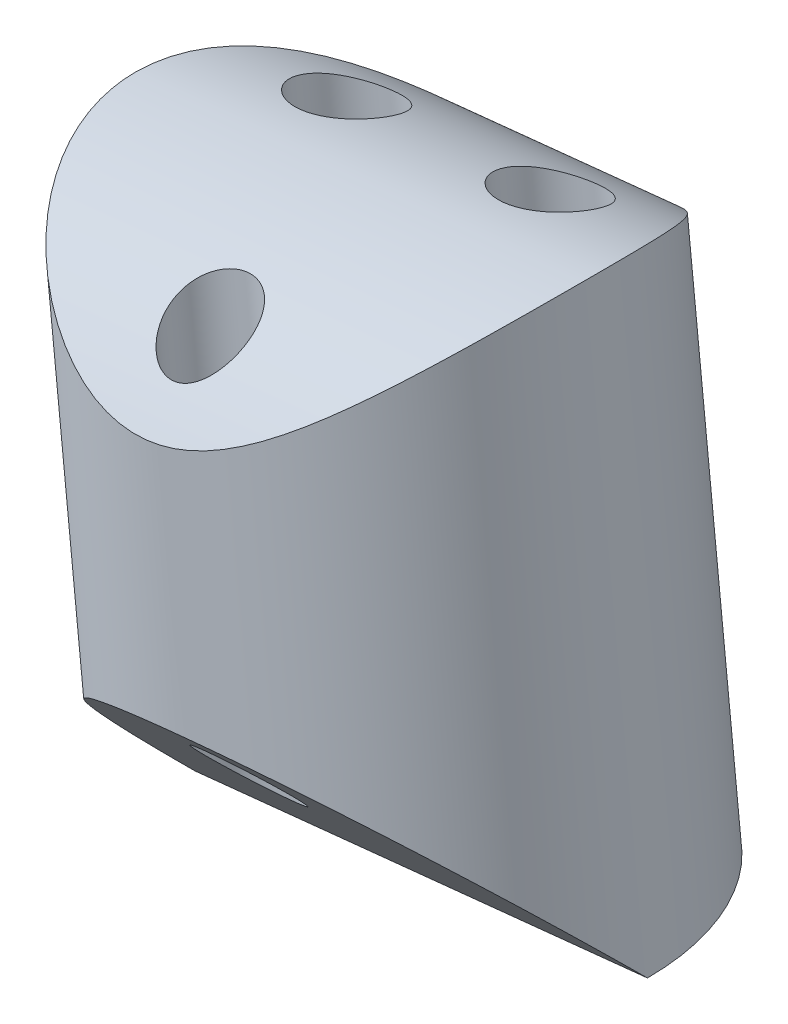
SolidWorks part; units mm, degrees
ref_plane "Front Plane" through (0, 0, 0) normal (0, 0, 1) x (1, 0, 0)
ref_plane "Top Plane" through (0, 0, 0) normal (0, 1, 0) x (1, 0, 0)
ref_plane "Right Plane" through (0, 0, 0) normal (1, 0, 0) x (0, 0, -1)
sketch "Sketch2" plane through (0, 0, 0) normal (0, 0, 1) x (1, 0, 0)
  line L0 (0, 0) -> (90, 0)
  line L1 (90, 0) -> (90, 120)
  line L2 (90, 120) -> (0, 120)
  line L3 (0, 120) -> (0, 0)
  line L4 (0, 120) -> (-10, 120)
  line L5 (-10, 120) -> (-10, 16.9491)
  line L6 (-10, 120) -> (57.5, 127)
  line L7 (57.5, 127) -> (90, 124)
  line L8 (90, 120) -> (99, 60)
  line L10 (90, 124) -> (90, 120)
  line L11 (5.9147, 0) -> (5.9147, -25)
  line L12 (5.9147, -25) -> (-4.0853, -25)
  line L13 (-4.0853, -29) -> (-4.0853, 0)
  line L14 (80, 0) -> (80, -25)
  line L15 (80, -25) -> (90, -25)
  line L16 (90, -29) -> (90, 0)
  line L17 (15.7927, 122.6748) -> (5.4776, 222.1414)
  line L18 (5.4776, 222.1414) -> (21.3923, 223.7918)
  line L19 (21.3923, 223.7918) -> (31.7073, 124.3252)
  line L20 (7.6492, 201.201) -> (23.5639, 202.8514)
  line L21 (10.9066, 169.7905) -> (26.8212, 171.441)
  line L22 (-10, 120) -> (-20.0396, 216.8108)
  line L23 (-20.0396, 216.8108) -> (-4.125, 218.4612)
  line L24 (-4.125, 218.4612) -> (5.9147, 121.6504)
  line L25 (-17.926, 196.4296) -> (-2.0114, 198.08)
  line L26 (-14.7556, 165.8578) -> (1.159, 167.5082)
  line L27 (57.5, 127) -> (46.9095, 229.1223)
  line L28 (46.9095, 229.1223) -> (30.9949, 227.4719)
  line L29 (30.9949, 227.4719) -> (41.5853, 125.3496)
  line L30 (33.2245, 205.9725) -> (49.1391, 207.6229)
  line L31 (36.5688, 173.7233) -> (52.4835, 175.3737)
  line L34 (90, 124) -> (99.1917, 223.5767)
  line L35 (99.1917, 223.5767) -> (83.2594, 225.0473)
  line L36 (83.2594, 225.0473) -> (74.0677, 125.4707)
  line L38 (81.3243, 204.0838) -> (97.2566, 202.6132)
  line L39 (78.4217, 172.6386) -> (94.354, 171.1679)
  line L40 (62.4078, 79.6749) -> (57.5, 127) construction
  line L41 (41.5853, 125.3496) -> (46.4931, 78.0244) construction
  line L42 (46.4931, 78.0244) -> (62.4078, 79.6749) construction
  line L43 (31.7073, 124.3252) -> (36.6151, 77.0001) construction
  line L44 (36.6151, 77.0001) -> (20.7005, 75.3496) construction
  line L45 (20.7005, 75.3496) -> (15.7927, 122.6748) construction
  line L46 (5.9147, 121.6504) -> (10.8224, 74.3253) construction
  line L47 (10.8224, 74.3253) -> (-5.0922, 72.6749) construction
  line L48 (-5.0922, 72.6749) -> (-10, 120) construction
  line L49 (74.0677, 125.4707) -> (69.6944, 78.0931) construction
  line L50 (69.6944, 78.0931) -> (85.7624, 78.0931) construction
  line L51 (85.7624, 78.0931) -> (90, 124) construction
  line L52 (-12.0823, 217.636) -> (10.4873, 0) construction
  line L53 (13.4349, 222.9666) -> (36.5574, 0) construction
  line L54 (38.9522, 228.2971) -> (62.6275, 0) construction
  line L55 (91.2256, 224.312) -> (70.5198, 0) construction
  line L59 (99, 60) -> (93.5277, 44.9649)
  line L60 (99, 60) -> (169.4769, 34.3485)
  line L61 (169.4769, 34.3485) -> (164.0046, 19.3134)
  line L62 (164.0046, 19.3134) -> (93.5277, 44.9649)
  line L63 (90, -2) -> (100, -2)
  line L64 (141.2862, 44.6091) -> (135.8138, 29.574)
  line L65 (99, 60) -> (55.7741, 75.7329) construction
  line L66 (55.7741, 75.7329) -> (50.3018, 60.6978) construction
  line L67 (100, -2) -> (100, -29)
  line L70 (-4.0853, -2) -> (-14.0853, -2)
  line L71 (-14.0853, -2) -> (-14.0853, -29)
  line L74 (-4.0853, 0) -> (0, 0)
  line L75 (-14.0853, -29) -> (-14.0853, -112.587)
  line L76 (-14.0853, -112.587) -> (100, -112.587)
  line L77 (100, -112.587) -> (100, -29)
  line L78 (-14.0853, -29) -> (100, -29)
  line L79 (-14.0853, -14.5) -> (100, -14.5) construction
  line L80 (31.7073, -112.587) -> (31.7073, -122.6232)
  line L81 (31.7073, -122.6232) -> (42.9573, -122.6232)
  line L82 (42.9573, -122.6232) -> (42.9573, -112.587)
  line L83 (-14.0853, -112.587) -> (-88.3667, -112.587)
  line L84 (-88.3667, -112.587) -> (-88.3667, -128.2699)
  line L85 (-88.3667, -128.2699) -> (169.4958, -128.2699)
  line L86 (169.4958, -128.2699) -> (169.4958, -112.587)
  line L87 (169.4958, -112.587) -> (100, -112.587)
  line L88 (90, 60) -> (-10, 60) construction
  line L89 (50.3018, 60.6978) -> (93.5277, 44.9649) construction
  line L90 (87.2806, 55.7521) -> (166.7408, 26.8309) construction
  line L91 (87.2806, 55.7521) -> (82.1749, 52.5336) construction
  line L92 (82.1749, 52.5336) -> (77.3257, 0) construction
  line L93 (83.1185, 56.6957) -> (86.337, 51.59) construction
  arc A0 (-10, 16.9491) -> (-4.0853, 0) centre (14.9876, 16.1624) ccw
  arc A1 (93.5277, 44.9649) -> (90, 0) centre (-126.4069, 39.5988) cw
  point P42 (41.1818, 206.7977)
  point P100 (84.7278, 54.1428)
  point P101 (84.7278, 54.1428)
  dimension "D11" = 47.3684
  dimension "D35" = 9
  dimension "D32" = 220
  dimension "D36" = 25
  dimension "D1" = 120
  dimension "D2" = 90
  dimension "D3" = 10
  dimension "D5" = 67.862
  dimension "D6" = 7
  dimension "D7" = 4
  dimension "D8" = 16
  dimension "D9" = 16
  dimension "D10" = 100
  dimension "D12" = 31.5789
  dimension "D13" = 16
  dimension "D14" = 16
  dimension "D15" = 16
  dimension "D16" = 25.7927
  dimension "D17" = 100
  dimension "D18" = 21.0526
  dimension "D19" = 31.5789
  dimension "D20" = 97.33
  dimension "D21" = 102.67
  dimension "D22" = 20.4905
  dimension "D23" = 30.7358
  dimension "D24" = 21.6147
  dimension "D25" = 32.4221
  dimension "D26" = 25
  dimension "D28" = 25
  dimension "D29" = 75
  dimension "D30" = 47.5789
  dimension "D31" = 30
  dimension "D33" = 46
  dimension "D34" = 20
  dimension "D37" = 2
  dimension "D38" = 2
  dimension "D39" = 27
  dimension "D40" = 10
  dimension "D41" = 10
  dimension "D42" = 27
  dimension "D43" = 14.5
  dimension "D44" = 127.5
ref_plane "Plane1" through (87.2806, 55.7521, 0) normal (-0.846, -0.5333, 0) x (0, 0, 1)
ref_plane "Plane2" through (82.1749, 52.5336, 0) normal (-0.0919, -0.9958, 0) x (-0.9958, 0.0919, 0)
ref_plane "Plane3" through (91.2256, 224.312, 0) normal (-0.0919, -0.9958, 0) x (-0.9958, 0.0919, 0)
ref_plane "Plane4" through (38.9522, 228.2971, 0) normal (0.1032, -0.9947, 0) x (-0.9947, -0.1032, 0)
ref_plane "Plane5" through (13.4349, 222.9666, 0) normal (0.1032, -0.9947, 0) x (-0.9947, -0.1032, 0)
ref_plane "Plane7" through (166.7408, 26.8309, 0) normal (0.9397, -0.342, 0) x (0, 0, -1)
ref_plane "Plane8" through (110.4217, -40.1902, 0) normal (0.9397, -0.342, 0) x (0, 0, -1)
ref_plane "Plane9" through (19.3664, 209.803, 0) normal (-0.0919, -0.9958, 0) x (-0.9958, 0.0919, 0)
ref_plane "Plane10" through (16.4638, 178.3578, 0) normal (-0.0919, -0.9958, 0) x (-0.9958, 0.0919, 0)
ref_plane "Plane11" through (-20.7793, 200.3721, 0) normal (0.1032, -0.9947, 0) x (-0.9947, -0.1032, 0)
ref_plane "Plane12" through (-17.435, 168.1229, 0) normal (0.1032, -0.9947, 0) x (-0.9947, -0.1032, 0)
ref_plane "Plane13" through (-20.5619, 198.2754, 0) normal (0.1032, -0.9947, 0) x (-0.9947, -0.1032, 0)
ref_plane "Plane14" through (-17.3045, 166.8649, 0) normal (0.1032, -0.9947, 0) x (-0.9947, -0.1032, 0)
ref_plane "Plane15" through (-12.0823, 217.636, 0) normal (0.1032, -0.9947, 0) x (-0.9947, -0.1032, 0)
ref_plane "Plane16" through (-20.3445, 196.1788, 0) normal (0.1032, -0.9947, 0) x (-0.9947, -0.1032, 0)
ref_plane "Plane17" through (-17.1741, 165.607, 0) normal (0.1032, -0.9947, 0) x (-0.9947, -0.1032, 0)
ref_plane "Plane18" through (12.1098, 131.1899, 0) normal (-0.0919, -0.9958, 0) x (-0.9958, 0.0919, 0)
ref_plane "Plane19" through (-12.4184, 119.7492, 0) normal (0.1032, -0.9947, 0) x (-0.9947, -0.1032, 0)
ref_plane "Plane20" through (0, 0, 0) normal (0, 0, 1) x (0.1032, -0.9947, 0)
ref_plane "Plane21" through (0, 0, 0) normal (0, 0, 1) x (-0.0919, -0.9958, 0)
ref_plane "Plane22" through (10.3758, 1.076, 0) normal (-0.9947, -0.1032, 0) x (0.1032, -0.9947, 0)
ref_plane "Plane23" through (36.1684, 3.7508, 0) normal (-0.9947, -0.1032, 0) x (0.1032, -0.9947, 0)
ref_plane "Plane24" through (61.9611, 6.4256, 0) normal (-0.9947, -0.1032, 0) x (0.1032, -0.9947, 0)
ref_plane "Plane25" through (69.924, -6.4545, 0) normal (-0.9958, 0.0919, 0) x (-0.0919, -0.9958, 0)
sketch "Sketch3" plane through (-12.0823, 217.636, 0) normal (0.1032, -0.9947, 0) x (-0.9947, -0.1032, 0)
  circle A0 centre (0, 0) radius 8
  dimension "D1" = 16
extrude "Boss-Extrude1" add sketch "Sketch3" along normal blind 20.4905
sketch "Sketch4" plane through (10.3758, 1.076, 0) normal (-0.9947, -0.1032, 0) x (0.1032, -0.9947, 0)
  line L0 (-217.7214, 8) -> (-213.7214, 8)
  line L1 (-197.2309, 8) -> (-217.7214, 8) construction
  line L2 (-217.7214, 8) -> (-217.7214, -8)
  line L3 (-217.7214, -8) -> (-213.7214, -8)
  line L4 (-217.7214, -8) -> (-197.2309, -8) construction
  arc A0 (-213.7214, 8) -> (-213.7214, -8) centre (-207.3937, 0) ccw
  dimension "D2" = 10.2
  dimension "D1" = 4
extrude "Cut-Extrude1" cut sketch "Sketch4" against normal through all and the other way through all
sketch "Sketch5" plane through (10.3758, 1.076, 0) normal (-0.9947, -0.1032, 0) x (0.1032, -0.9947, 0)
  line L0 (-197.2309, 0) -> (-205.2309, 8)
  line L1 (-197.2309, -8) -> (-197.2309, 8) construction
  line L2 (-197.2309, 8) -> (-213.7214, 8) construction
  line L3 (-205.2309, 8) -> (-197.2309, 8)
  line L4 (-197.2309, 8) -> (-197.2309, 0)
  dimension "D1" = 45
extrude "Cut-Extrude2" cut sketch "Sketch5" against normal through all and the other way through all
sketch "Sketch7" plane through (10.3758, 1.076, 0) normal (-0.9947, -0.1032, 0) x (0.1032, -0.9947, 0)
  line L2 (-193.2309, 0) -> (-197.2309, -4)
  line L5 (-201.2309, 4) -> (-197.2309, 0)
  line L6 (-197.2309, 0) -> (-205.2309, 8) construction
  line L8 (-213.7055, 0) -> (7.2742, 0) construction
  line L9 (-193.2309, 0) -> (-193.2309, 4)
  line L10 (-193.2309, 4) -> (-201.2309, 4)
  line L11 (-197.2309, 0) -> (-193.2309, 4) construction
  line L12 (-197.2309, -8) -> (-197.2309, 0) construction
  line L13 (-197.2309, 0) -> (-197.2309, -4)
  dimension "D1" = 45
sketch "Sketch8" plane through (-12.0823, 217.636, 0) normal (0.1032, -0.9947, 0) x (-0.9947, -0.1032, 0)
  line L0 (8, 0) -> (-8, 0) construction
  circle A0 centre (-3.6, 3) radius 1.6
  circle A1 centre (3.6, 3) radius 1.6
  circle A3 centre (0, -5.5) radius 1.4
  point P6 (0, 0)
  dimension "D1" = 3.2
  dimension "D2" = 3.2
  dimension "D7" = 2.8
  dimension "D3" = 3
  dimension "D4" = 3
  dimension "D5" = 3.6
  dimension "D6" = 3.6
  dimension "D8" = 5.5
extrude "Cut-Extrude3" cut sketch "Sketch8" against normal through all and the other way through all
sketch "Sketch9" plane through (-20.3445, 196.1788, 0) normal (0.1032, -0.9947, 0) x (0.9947, 0.1032, 0)
  line L0 (4.5289, -5.4) -> (16.3339, -5.4)
  line L1 (2.4314, 0) -> (18.4314, 0) construction
  arc A0 (2.4314, 0) -> (18.4314, 0) centre (10.4314, 0) ccw construction
  arc A1 (4.5289, -5.4) -> (16.3339, -5.4) centre (10.4314, 0) ccw
  dimension "D1" = 5.4
